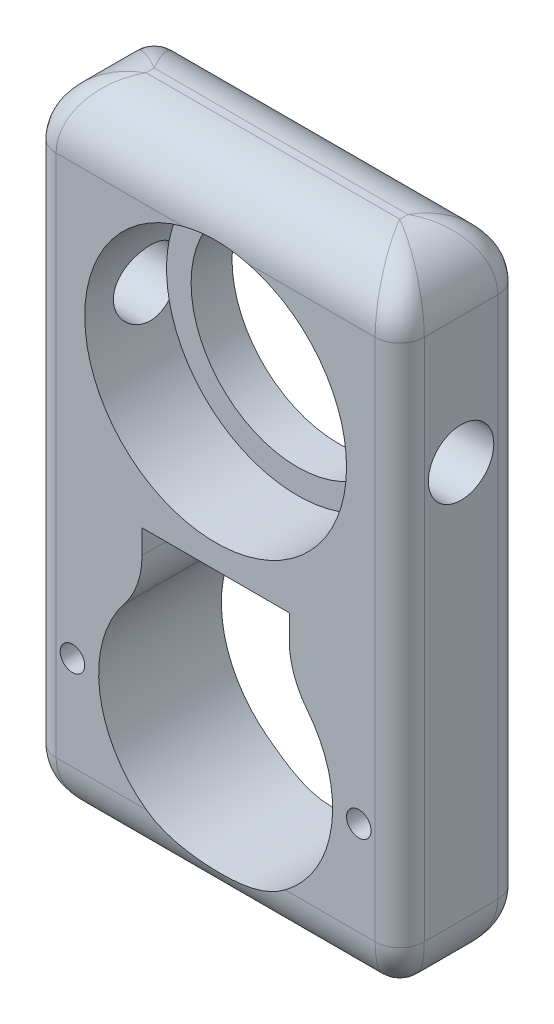
SolidWorks part; units mm, degrees
ref_plane "Front Plane" through (0, 0, 0) normal (0, 0, 1) x (1, 0, 0)
ref_plane "Top Plane" through (0, 0, 0) normal (0, 1, 0) x (1, 0, 0)
ref_plane "Right Plane" through (0, 0, 0) normal (1, 0, 0) x (0, 0, -1)
sketch "Sketch1" plane through (0, 0, 0) normal (0, 0, 1) x (1, 0, 0)
  line L0 (22.5, 45) -> (22.5, 0) construction
  line L1 (0, 0) -> (45, 0)
  line L2 (0, 0) -> (0, 45)
  line L3 (0, 45) -> (45, 45)
  line L4 (45, 0) -> (45, 45)
  circle A0 centre (22.5, 22.5) radius 16
extrude "Boss-Extrude1" add sketch "Sketch1" along normal blind 15
sketch "Sketch2" plane through (45, 0, 0) normal (1, 0, 0) x (0, 0, -1)
  line L0 (-15, 22.5) -> (0, 22.5) construction
  line L1 (-15, 0) -> (-15, 45) construction
  line L2 (0, 0) -> (0, 45) construction
  circle A0 centre (-7.5, 22.5) radius 4
extrude "Cut-Extrude1" cut sketch "Sketch2" against normal through all
sketch "Sketch4" plane through (0, 0, 0) normal (0, 0, -1) x (-1, 0, 0)
  circle A0 centre (-22.5, 22.5) radius 16
  circle A1 centre (-22.5, 22.5) radius 13
  dimension "D1" = 3
extrude "Boss-Extrude3" add sketch "Sketch4" against normal blind 5
sketch "Esboço3" plane through (0, 0, 0) normal (0, -1, 0) x (-1, 0, 0)
  line L1 (-45, -15) -> (0, -15)
  line L2 (-45, -15) -> (-45, 0)
  line L3 (-45, 0) -> (0, 0)
  line L4 (0, -15) -> (0, 0)
extrude "Ressalto-extrusão2" add sketch "Esboço3" along normal blind 33
sketch "Esboço4" plane through (0, 0, 15) normal (0, 0, 1) x (1, 0, 0)
  line L0 (22.5, 6.5) -> (22.5, -22.5) construction
  line L1 (22.5, -28.8) -> (22.5, -9.5)
  line L2 (22.5, -0.2) -> (22.5, 3.5813)
  line L3 (31.5, -3.3874) -> (31.5, 3.5813)
  line L4 (13.5, -3.3874) -> (13.5, 3.5813)
  line L5 (13.5, -0.2) -> (13.5, 3.5813) construction
  line L6 (31.5, -0.2) -> (31.5, 3.5813) construction
  line L7 (5, -14.5) -> (22.5, -14.5) construction
  line L8 (13.5, 3.5813) -> (31.5, 3.5813)
  arc A0 (6.8076, 19.3775) -> (38.1924, 19.3775) centre (22.5, 22.5) ccw construction
  circle A1 centre (22.5, -14.5) radius 14.3
  circle A2 centre (5, -14.5) radius 1.5
  circle A3 centre (40, -14.5) radius 1.5
  point P10 (33.5, -31.5813)
  point P11 (33.5, -9.5)
  point P12 (11.5, -31.5813)
  point P13 (11.5, -9.5)
  dimension "D2" = 8
  dimension "D1" = 29
  dimension "D3" = 9
  dimension "D4" = 9
extrude "Corte-extrusão1" cut sketch "Esboço4" against normal through all contours A1 | A3 | A2 | A1 L2 L8 L4 | A1 L3 L8 L2 region at (17.5144, 1.095, 15) region at (27.4856, 1.095, 15) region at (27.1388, -1.4016, 15) region at (5, -14.5, 15) region at (40, -14.5, 15)
fillet "Filete1" radius 10 2 edges at (31.5, -3.3874, 7.5) (13.5, -3.3874, 7.5)
fillet "Filete2" radius 3 4 edges at (0, 6, 0) (45, 6, 0) (45, 6, 15) (0, 6, 15)
fillet "Filete3" radius 7 16 edges at (44.1213, -33, 14.1213) (45, -33, 7.5) (44.1213, -33, 0.8787) (22.5, -33, 0) (0.8787, -33, 0.8787) (0, -33, 7.5) (0.8787, -33, 14.1213) (44.1213, 45, 14.1213) (45, 45, 7.5) (44.1213, 45, 0.8787) (22.5, 45, 0) (0.8787, 45, 0.8787) (0, 45, 7.5) (0.8787, 45, 14.1213) (22.5, -33, 15) (22.5, 45, 15)
